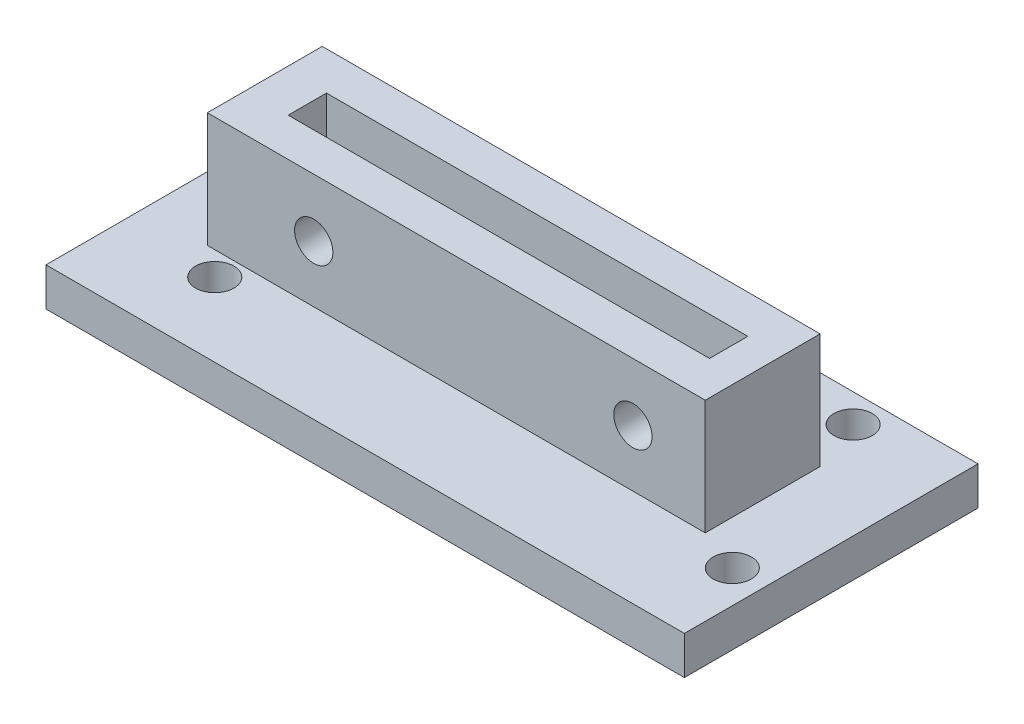
SolidWorks part; units mm, degrees
ref_plane "Front Plane" through (0, 0, 0) normal (0, 0, 1) x (1, 0, 0)
ref_plane "Top Plane" through (0, 0, 0) normal (0, 1, 0) x (1, 0, 0)
ref_plane "Right Plane" through (0, 0, 0) normal (1, 0, 0) x (0, 0, -1)
sketch "Sketch1" plane through (0, 0, 0) normal (0, 1, 0) x (1, 0, 0)
  line L1 (-21.7033, -10.0275) -> (28.2967, -10.0275)
  line L2 (-21.7033, -10.0275) -> (-21.7033, 12.9725)
  line L3 (-21.7033, 12.9725) -> (28.2967, 12.9725)
  line L4 (28.2967, -10.0275) -> (28.2967, 12.9725)
  circle A0 centre (-19.2623, 10.7488) radius 1.5
  circle A1 centre (20.7377, 10.7488) radius 1.5
  circle A2 centre (25.7369, -3.7123) radius 1.5
  circle A3 centre (-14.2631, -4.2512) radius 1.5
  dimension "D3" = 3
  dimension "D4" = 3
  dimension "D5" = 3
  dimension "D6" = 3
  dimension "D1" = 50
  dimension "D2" = 23
  dimension "D7" = 40
  dimension "D8" = 15
  dimension "D9" = 40
extrude "Boss-Extrude1" add sketch "Sketch1" along normal blind 3
sketch "Sketch2" plane through (0, 3, 0) normal (0, 1, 0) x (1, 0, 0)
  line L0 (-21.7033, 12.9725) -> (-21.7033, -10.0275) construction
  line L1 (-16.7033, 6.6089) -> (22.2967, 6.6089)
  line L2 (-16.7033, 6.6089) -> (-16.7033, -2.3911)
  line L3 (-16.7033, -2.3911) -> (22.2967, -2.3911)
  line L4 (22.2967, 6.6089) -> (22.2967, -2.3911)
  line L5 (-13.3699, 3.6089) -> (19.6301, 3.6089)
  line L6 (-13.3699, 3.6089) -> (-13.3699, 0.6089)
  line L7 (-13.3699, 0.6089) -> (19.6301, 0.6089)
  line L8 (19.6301, 3.6089) -> (19.6301, 0.6089)
  dimension "D1" = 3
  dimension "D2" = 3
  dimension "D3" = 3
  dimension "D4" = 33
  dimension "D5" = 39
  dimension "D6" = 5
extrude "Boss-Extrude2" add sketch "Sketch2" along normal blind 9
sketch "Sketch3" plane through (0, 0, 2.3911) normal (0, 0, 1) x (1, 0, 0)
  line L0 (-13.3699, 12) -> (-13.3699, 3) construction
  line L1 (-13.3699, 12) -> (-13.3699, 3) construction
  circle A0 centre (-8.3699, 7.4481) radius 1.5
  circle A1 centre (16.6301, 7.4481) radius 1.5
  dimension "D1" = 3
  dimension "D2" = 3
  dimension "D3" = 25
  dimension "D4" = 5
extrude "Cut-Extrude1" cut sketch "Sketch3" against normal through all
equation "\"A\"=9.9176"
